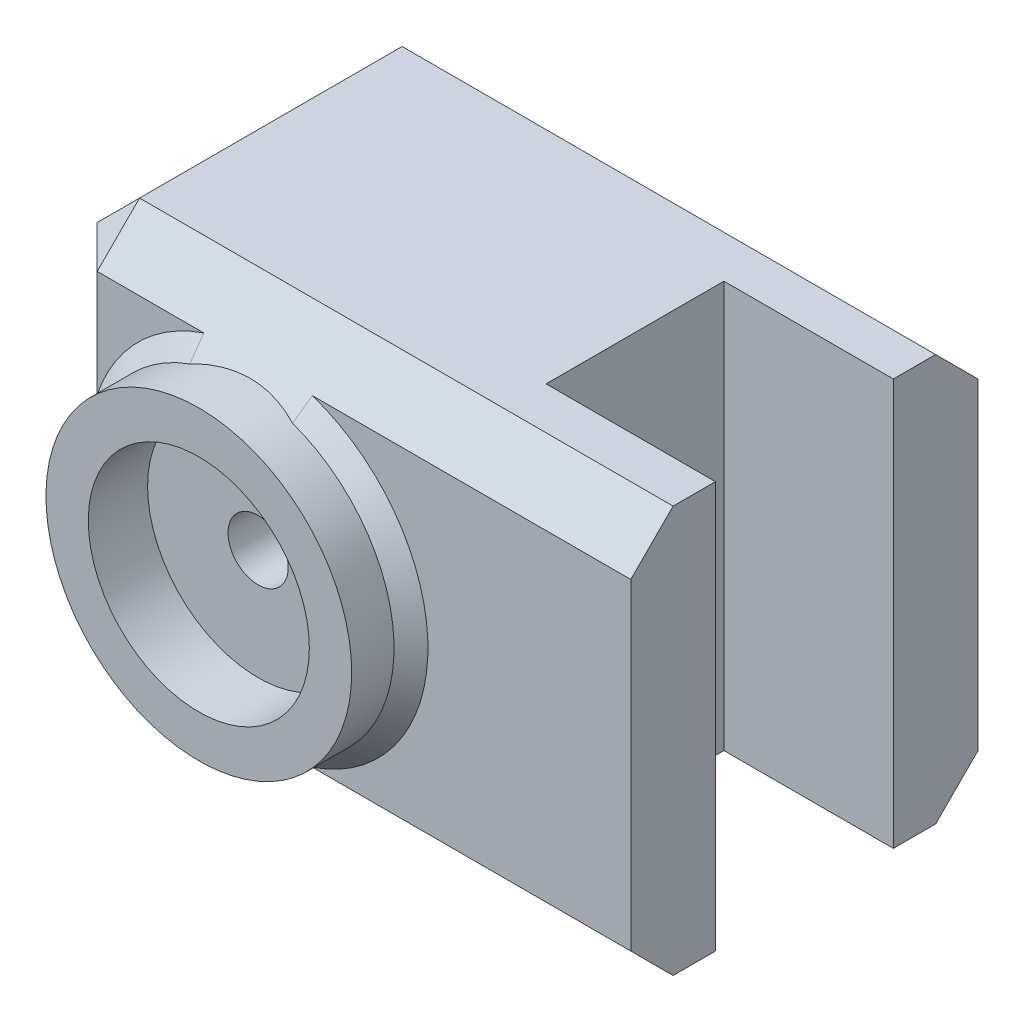
SolidWorks part; units mm, degrees
ref_plane "Front Plane" through (0, 0, 0) normal (0, 0, 1) x (1, 0, 0)
ref_plane "Top Plane" through (0, 0, 0) normal (0, 1, 0) x (1, 0, 0)
ref_plane "Right Plane" through (0, 0, 0) normal (1, 0, 0) x (0, 0, -1)
sketch "Sketch1" plane through (0, 0, 0) normal (0, 1, 0) x (1, 0, 0)
  line L0 (10, -10.5) -> (10, -20.5)
  line L1 (-10, -10.5) -> (10, -10.5)
  line L2 (-10, -10.5) -> (-10, 10.5)
  line L3 (-10, 10.5) -> (10, 10.5)
  line L5 (-10, -10.5) -> (10, 10.5) construction
  line L6 (-10, 10.5) -> (10, -10.5) construction
  line L7 (10, -20.5) -> (-58, -20.5)
  line L8 (-58, -20.5) -> (-58, 20.5)
  line L9 (10, 10.5) -> (10, 20.5)
  line L10 (10, 20.5) -> (-58, 20.5)
  line L11 (0, 0) -> (-47.1613, 0) construction
  point P0 (0, 0)
  point P13 (-58, 0)
  dimension "D1" = 21
  dimension "D2" = 20
  dimension "D3" = 10
  dimension "D4" = 48
extrude "Boss-Extrude1" add sketch "Sketch1" along normal blind 48
sketch "Sketch2" plane through (0, 0, -20.5) normal (0, 0, -1) x (-1, 0, 0)
  line L0 (-10, 48) -> (58, 48) construction
  line L1 (58, 0) -> (10, 0)
  line L2 (58, 0) -> (58, 48)
  line L3 (58, 48) -> (10, 48)
  line L4 (10, 0) -> (10, 48)
  line L5 (-10, 48) -> (-10, 0) construction
  line L6 (58, 24) -> (10, 24) construction
  line L7 (10, 24) -> (34, 24) construction
  line L8 (34, 24) -> (34, 48) construction
  circle A0 centre (34, 24) radius 13.05
  dimension "D2" = 26.1
  dimension "D1" = 20
extrude "Cut-Extrude1" cut sketch "Sketch2" against normal blind 7 contours A0 | A0 region at (-34, 24, -20.5)
sketch "Sketch3" plane through (0, 0, -13.5) normal (0, 0, -1) x (-1, 0, 0)
  circle A0 centre (34, 24) radius 3.5516
  circle A1 centre (34, 24) radius 13.05 construction
extrude "Cut-Extrude2" cut sketch "Sketch3" against normal blind 48
chamfer "Chamfer1" distance 5 angle 45 8 edges at (-24, 0, -20.5) (-24, 48, 20.5) (-24, 48, -20.5) (-58, 24, -20.5) (-58, 48, 0) (-58, 24, 20.5) (-58, 0, 0) (-24, 0, 20.5)
sketch "Sketch4" plane through (0, 0, 20.5) normal (0, 0, 1) x (1, 0, 0)
  circle A0 centre (-34, 24) radius 13.05
  circle A1 centre (-34, 24) radius 18.05
  dimension "D1" = 26.1
  dimension "D2" = 5
extrude "Boss-Extrude2" add sketch "Sketch4" along normal blind 7
chamfer "Chamfer2" distance 2 angle 45 1 edges at (-52.05, 24, 20.5)
sketch "Sketch6" plane through (0, 0, -10.5) normal (0, 0, 1) x (1, 0, 0)
  line L0 (0, -0.612) -> (0, 62.4943) construction
